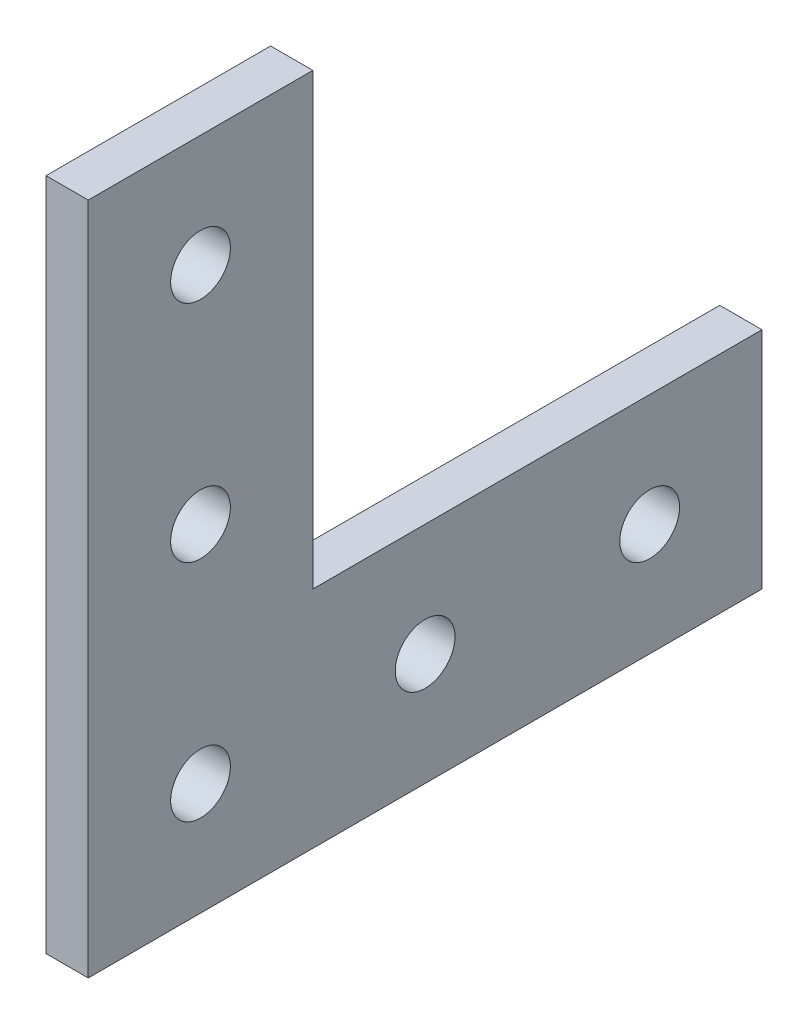
SolidWorks part; units mm, degrees
material "5052-H36"
ref_plane "Front" through (0, 0, 0) normal (0, 0, 1) x (1, 0, 0)
ref_plane "Top" through (0, 0, 0) normal (0, 1, 0) x (1, 0, 0)
ref_plane "Right" through (0, 0, 0) normal (1, 0, 0) x (0, 0, -1)
ref_axis "Axis1" through (0, 0, 55) along (0, 0, -1)
sketch "Sketch1" plane through (0, 0, 0) normal (1, 0, 0) x (0, 0, -1)
  line L0 (0, 0) -> (0, 50.8)
  line L1 (0, 0) -> (50.8, 0)
  line L2 (-25.4, -25.4) -> (50.8, -25.4)
  line L3 (-25.4, -25.4) -> (-25.4, 50.8)
  line L4 (-25.4, 50.8) -> (0, 50.8)
  line L5 (50.8, 0) -> (50.8, -25.4)
  dimension "D1" = 76.2
  dimension "D2" = 25.4
extrude "Boss-Extrude1" add sketch "Sketch1" along normal blind 4.7752
hole_wizard "1/4 Clearance Hole1" positions "Sketch2" profile "Sketch3" hole size "1/4" standard "ANSI Inch"
sketch "Sketch2" plane through (4.7752, 0, 0) normal (1, 0, 0) x (0, 0, -1)
  line L0 (-12.7, 50.8) -> (-12.7, -25.4) construction
  line L1 (0, 50.8) -> (-25.4, 50.8) construction
  line L2 (-25.4, -25.4) -> (50.8, -25.4) construction
  line L4 (50.8, -12.7) -> (-25.4, -12.7) construction
  line L5 (50.8, -25.4) -> (50.8, 0) construction
  line L6 (-25.4, 50.8) -> (-25.4, -25.4) construction
  point P0 (-12.7, -12.7)
  point P20 (12.7, -12.7)
  point P22 (38.1, -12.7)
  point P24 (-12.7, 12.7)
  point P26 (-12.7, 38.1)
  dimension "D1" = 25.4
  dimension "D2" = 25.4
  dimension "D3" = 25.4
  dimension "D4" = 25.4
sketch "Sketch3" plane through (4.7752, -12.7, 12.7) normal (0, 1, 0) x (0, 0, -1)
  line L0 (0, 0) -> (0, 16.5078)
  line L1 (0, 16.5078) -> (3.3782, 14.478)
  line L2 (3.3782, 14.478) -> (3.3782, 0)
  line L5 (3.3782, 0) -> (0, 0)
  line L10 (0, 16.5078) -> (-3.3782, 14.478) construction
  line L11 (0, -6.35) -> (0, 107.95) construction
  dimension "Hole Dia." = 6.7564
  dimension "Hole Depth" = 14.478
  dimension "Drill Angle" = 118
